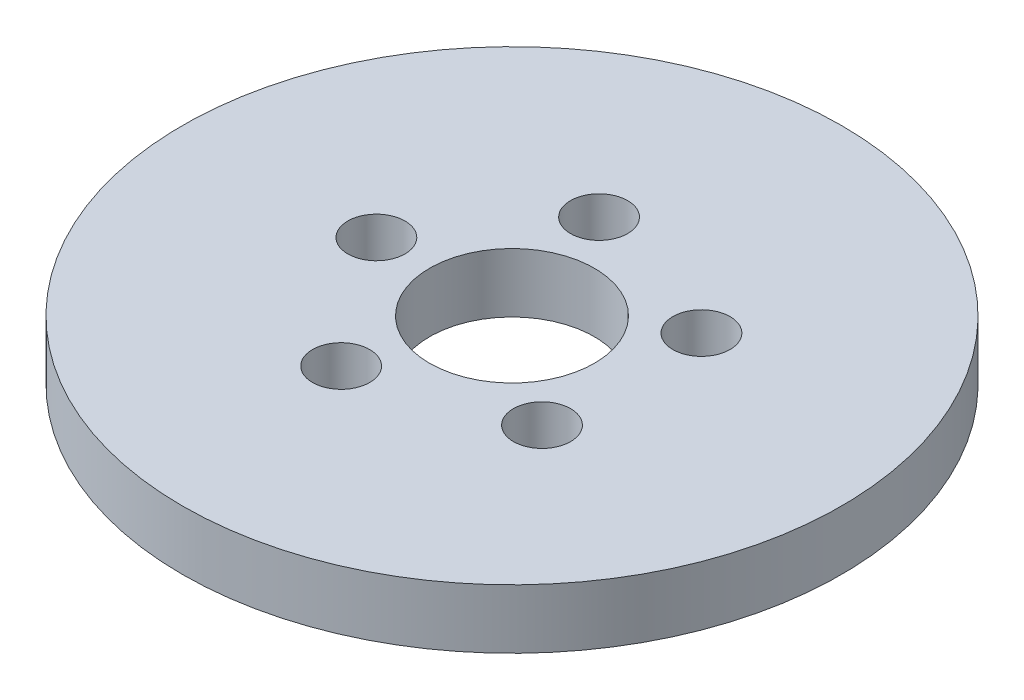
SolidWorks part; units mm, degrees
ref_plane "Front Plane" through (0, 0, 0) normal (0, 0, 1) x (1, 0, 0)
ref_plane "Top Plane" through (0, 0, 0) normal (0, 1, 0) x (1, 0, 0)
ref_plane "Right Plane" through (0, 0, 0) normal (1, 0, 0) x (0, 0, -1)
sketch "Sketch1" plane through (0, 0, 0) normal (0, 1, 0) x (1, 0, 0)
  circle A0 centre (0, 0) radius 100
  dimension "FLANGE_OD" = 200
extrude "Boss-Extrude1" add sketch "Sketch1" along normal blind 18
sketch "Sketch2" plane through (0, 0, 0) normal (0, 1, 0) x (1, 0, 0)
  circle A0 centre (0, 0) radius 25
  dimension "BORE_D" = 50
extrude "Cut-Extrude1" cut sketch "Sketch2" along normal through all
sketch "Sketch3" plane through (0, 18, 0) normal (0, 1, 0) x (1, 0, 0)
  circle A0 centre (0, 0) radius 41.1492 construction
  circle A1 centre (-41.1492, 0) radius 8.6745
  dimension "BOLT_D" = 17.349
  dimension "BOLT_PCD" = 82.2983
extrude "Cut-Extrude2" cut sketch "Sketch3" against normal blind 17.4133
pattern_circular "CirPattern1" count 5 over 360 about axis through (0, 0, 0) along (0, 1, 0) of "Cut-Extrude2"
